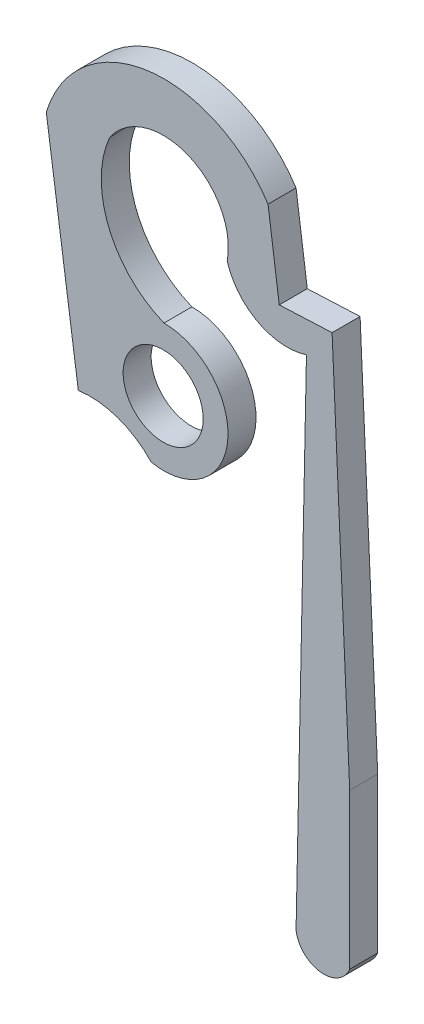
SolidWorks part; units mm, degrees
material "AISI 4340 Steel, normalized"
ref_plane "Front Plane" through (0, 0, 0) normal (0, 0, 1) x (1, 0, 0)
ref_plane "Top Plane" through (0, 0, 0) normal (0, 1, 0) x (1, 0, 0)
ref_plane "Right Plane" through (0, 0, 0) normal (1, 0, 0) x (0, 0, -1)
sketch "Sketch1" plane through (0, 0, 0) normal (0, 0, 1) x (1, 0, 0)
  line L0 (0.2144, 4.0365) -> (4.2844, 4.0365) construction
  line L1 (-33.8127, -4.8254) -> (30.8628, -4.8254) construction
  line L2 (-4.5226, 7.9647) -> (-3.5066, 0.8273)
  line L3 (2.5132, 8.9553) -> (2.8688, 6.3645)
  line L4 (2.8688, 6.3645) -> (4.5452, 6.4407)
  line L5 (4.5452, 6.4407) -> (5.104, -5.8529)
  line L6 (5.104, -10.7707) -> (5.104, -5.8529)
  line L7 (3.7324, 5.4247) -> (3.4022, -10.5519)
  arc A0 (2.5132, 8.9553) -> (-4.5226, 7.9647) centre (-0.7765, 6.839) ccw
  arc A1 (-3.5066, 0.8273) -> (-1.1952, 0.0145) centre (-3.1368, -1.8139) cw
  arc A2 (-1.1952, 0.0145) -> (-0.7888, 4.0375) centre (-0.7888, 2.0055) ccw
  arc A3 (-0.7888, 4.0375) -> (-2.516, 8.2695) centre (0.4219, 7) cw
  arc A4 (-2.516, 8.2695) -> (1.2178, 6.7455) centre (-0.8035, 7.1292) cw
  arc A5 (1.2178, 6.7455) -> (3.7324, 5.4247) centre (3.1175, 7.3081) ccw
  arc A6 (3.4022, -10.5519) -> (5.104, -10.7707) centre (4.2828, -10.4302) ccw
  circle A7 centre (-0.8142, 2.0211) radius 1.27
  point P26 (0, 0)
  point P27 (0, 0)
  point P28 (0, 0)
  dimension "D1" = 6.2484
  dimension "D2" = 2.032
  dimension "D3" = 2.667
  dimension "D4" = 2.0066
  dimension "D5" = 1.1938
  dimension "D6" = 0.381
  dimension "D8" = 3.7084
  dimension "D9" = 5.9436
  dimension "D10" = 1.7018
  dimension "D11" = 3.2004
  dimension "D13" = 3.9116
  dimension "D15" = 0.0254
  dimension "D18" = 2.0574
  dimension "D20" = 3.4036
  dimension "D21" = 1.9812
  dimension "D23" = 3.683
  dimension "D27" = 5.9182
  dimension "D29" = 4.2164
  dimension "D30" = 0.889
  dimension "D31" = 4.0365
  dimension "D7" = 2.6924
  dimension "D12" = 3.3274
  dimension "D14" = 6.9342
  dimension "D16" = 2.032
  dimension "D17" = 4.7244
  dimension "D19" = 4.5466
  dimension "D22" = 4.3434
  dimension "D24" = 5.334
  dimension "D25" = 4.4196
  dimension "D26" = 12.7762
  dimension "D28" = 12.573
  dimension "D32" = 4.8254
extrude "Boss-Extrude1" add sketch "Sketch1" along normal blind 0.889
